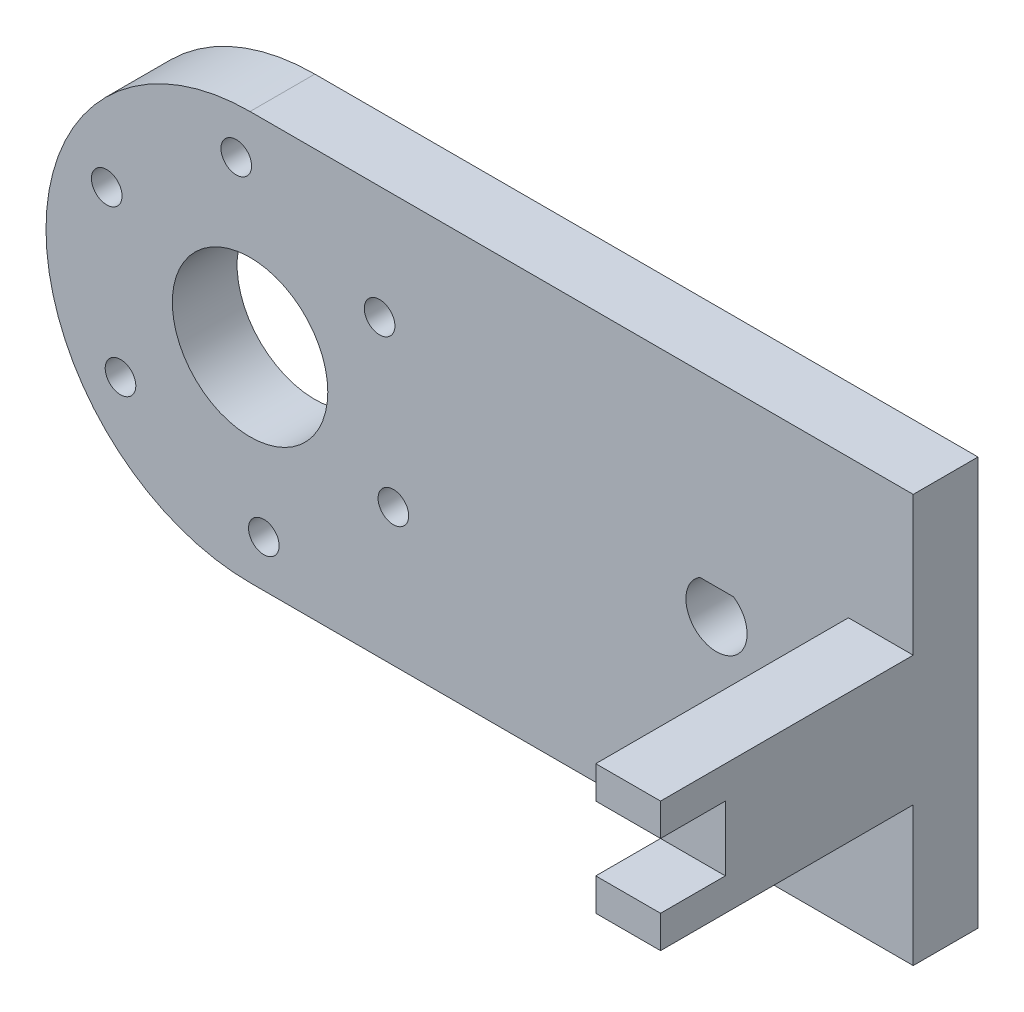
SolidWorks part; units mm, degrees
ref_plane "Front Plane" through (0, 0, 0) normal (0, 0, 1) x (1, 0, 0)
ref_plane "Top Plane" through (0, 0, 0) normal (0, 1, 0) x (1, 0, 0)
ref_plane "Right Plane" through (0, 0, 0) normal (1, 0, 0) x (0, 0, -1)
sketch "Sketch1" plane through (0, 0, 0) normal (0, 0, 1) x (1, 0, 0)
  line L1 (0, 20) -> (65, 20)
  line L2 (0, 20) -> (0, -20)
  line L3 (0, -20) -> (65, -20)
  line L4 (65, 20) -> (65, -20)
  circle A0 centre (0, 0) radius 20
  dimension "D1" = 40
  dimension "D2" = 65
extrude "Boss-Extrude1" add sketch "Sketch1" along normal blind 6.35 contours L2 L1 L4 L3 | A0
sketch "Sketch2" plane through (0, 0, 6.35) normal (0, 0, 1) x (1, 0, 0)
  line L0 (0, 0) -> (0, 15.5) construction
  line L1 (0, 0) -> (-1.3509, 15.441) construction
  line L2 (0, 0) -> (1.3509, -15.441) construction
  circle A0 centre (0, 0) radius 7.62
  circle A1 centre (0, 0) radius 15.5 construction
  circle A2 centre (-1.3509, 15.441) radius 1.5
  circle A3 centre (12.6969, 8.8904) radius 1.5
  circle A4 centre (14.0478, -6.5506) radius 1.5
  circle A5 centre (1.3509, -15.441) radius 1.5
  circle A6 centre (-12.6969, -8.8904) radius 1.5
  circle A7 centre (-14.0478, 6.5506) radius 1.5
  point P20 (0, 0)
  dimension "D1" = 15.24
  dimension "D2" = 31
  dimension "D4" = 3
  dimension "D3" = 5
  dimension "D5" = 6
extrude "Cut-Extrude1" cut sketch "Sketch2" against normal through all
ref_plane "Plane1" through (0, 0, 0) normal (0, 1, 0) x (1, 0, 0)
sketch "Sketch4" plane through (0, 0, 0) normal (0, 1, 0) x (1, 0, 0)
  line L1 (65, -6.35) -> (58.65, -6.35)
  line L2 (65, -6.35) -> (65, -31.115)
  line L3 (65, -31.115) -> (58.65, -31.115)
  line L4 (58.65, -6.35) -> (58.65, -31.115)
  dimension "D1" = 6.35
  dimension "D2" = 24.765
extrude "Boss-Extrude2" add sketch "Sketch4" along normal mid plane 12.7
sketch "Sketch5" plane through (65, 0, 0) normal (1, 0, 0) x (0, 0, -1)
  line L0 (-31.115, 6.35) -> (-31.115, -6.35) construction
  line L1 (-31.115, 3.175) -> (-24.765, 3.175)
  line L2 (-31.115, 3.175) -> (-31.115, -3.175)
  line L3 (-31.115, -3.175) -> (-24.765, -3.175)
  line L4 (-24.765, 3.175) -> (-24.765, -3.175)
  line L5 (0, 0) -> (-31.115, 0) construction
  line L6 (20.3625, 0) -> (-20.3625, 0) construction
  point P11 (-24.765, 0)
  dimension "D1" = 6.35
  dimension "D2" = 6.35
extrude "Cut-Extrude2" cut sketch "Sketch5" against normal up to next
sketch "Sketch6" plane through (0, 0, 0) normal (0, 0, -1) x (-1, 0, 0)
  line L0 (-65, 0) -> (0, 0) construction
  line L1 (-65, 20) -> (-65, -20) construction
  line L2 (-47.3783, 2.5) -> (-44.0617, 2.5)
  arc A0 (-47.3783, 2.5) -> (-44.0617, 2.5) centre (-45.72, 0) ccw
  point P9 (-45.72, -3)
  dimension "D1" = 6
  dimension "D2" = 45.72
  dimension "D3" = 5.5
extrude "Cut-Extrude3" cut sketch "Sketch6" against normal up to next
sketch "Sketch7" plane through (0, 0, 0) normal (0, 0, -1) x (-1, 0, 0)
  line L0 (-45.72, 13.5) -> (-45.72, 17.5) construction
  circle A0 centre (-45.72, 0) radius 15.5 construction
  arc A1 (-47.3783, 2.5) -> (-44.0617, 2.5) centre (-45.72, 0) ccw construction
  circle A2 centre (-45.72, 0) radius 13.5
  circle A3 centre (-45.72, 0) radius 17.5
  point P9 (-45.72, 15.5)
  point P10 (-45.72, 15.5)
  dimension "D1" = 31
  dimension "D2" = 4
extrude "Cut-Extrude4" cut sketch "Sketch7" against normal blind 2
